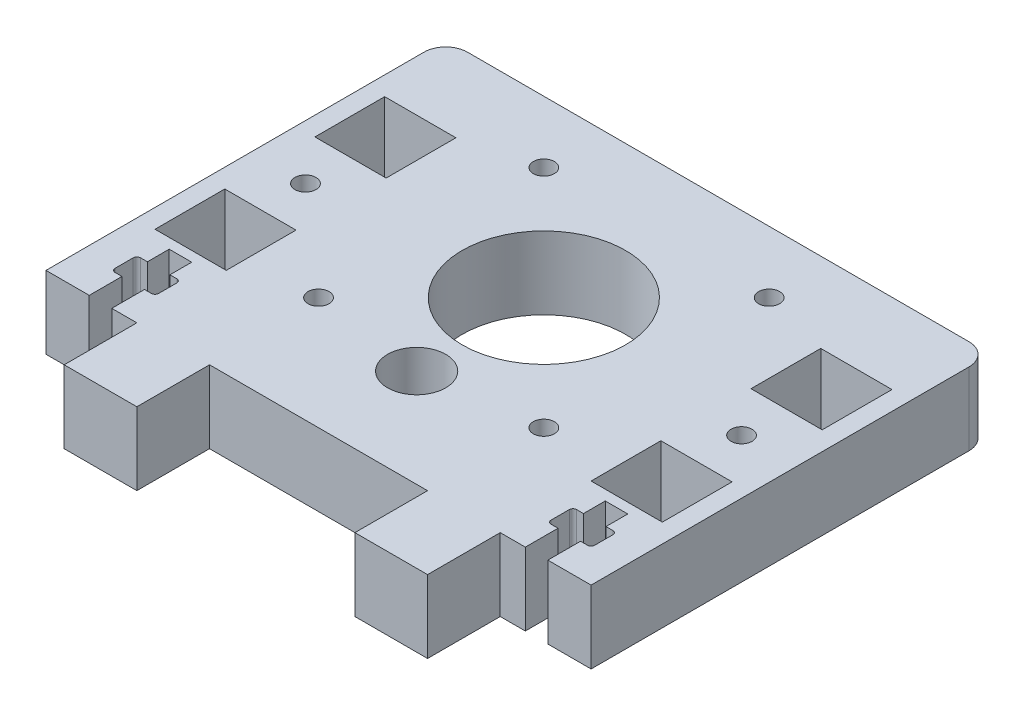
SolidWorks part; units mm, degrees
ref_plane "Front Plane" through (0, 0, 0) normal (0, 0, 1) x (1, 0, 0)
ref_plane "Top Plane" through (0, 0, 0) normal (0, 1, 0) x (1, 0, 0)
ref_plane "Right Plane" through (0, 0, 0) normal (1, 0, 0) x (0, 0, -1)
sketch "Sketch1" plane through (0, 0, 0) normal (0, 1, 0) x (1, 0, 0)
  line L0 (0, 29) -> (0, -8.5) construction
  line L1 (-34.5, 29) -> (0, 29)
  line L2 (-37.5, 26) -> (-37.5, -26)
  line L3 (-37.5, -26) -> (-25, -26)
  line L4 (0, 29) -> (0, 16.25)
  line L5 (0, -6.25) -> (0, -8.5)
  line L6 (0, -16.5) -> (0, -26) construction
  line L7 (-11.25, 5) -> (0, 5) construction
  line L8 (0, -16.5) -> (0, -26)
  line L9 (-30, 18) -> (-30, 8.4) construction
  line L10 (-37.5, 2.2) -> (0, 2.2) construction
  line L11 (-34.9, 18) -> (-25.1, 18)
  line L12 (-34.9, 18) -> (-34.9, 8.4)
  line L13 (-34.9, 8.4) -> (-25.1, 8.4)
  line L14 (-25.1, 18) -> (-25.1, 8.4)
  line L15 (-34.9, 18) -> (-25.1, 8.4) construction
  line L16 (-34.9, 8.4) -> (-25.1, 18) construction
  line L17 (-34.9, -4) -> (-25.1, -13.6) construction
  line L18 (-34.9, -13.6) -> (-25.1, -4) construction
  line L19 (-25.1, -13.6) -> (-25.1, -4)
  line L20 (-34.9, -4) -> (-25.1, -4)
  line L21 (-34.9, -13.6) -> (-34.9, -4)
  line L22 (-34.9, -13.6) -> (-25.1, -13.6)
  line L23 (-30, -4) -> (-30, -13.6) construction
  line L24 (-30, -8.8) -> (-30, 13.2) construction
  line L25 (0, 5) -> (-15.5, 20.5) construction
  line L35 (-15, -26) -> (0, -26)
  line L43 (-20, -36) -> (-20, -24.6) construction
  line L44 (-15, -26) -> (-15, -36)
  line L45 (-15, -36) -> (-25, -36)
  line L46 (-25, -36) -> (-25, -26)
  arc A1 (-34.5, 29) -> (-37.5, 26) centre (-34.5, 26) ccw
  arc A2 (0, 16.25) -> (0, -6.25) centre (0, 5) ccw
  circle A4 centre (-15.5, 20.5) radius 1.45
  circle A6 centre (-15.5, -10.5) radius 1.45
  circle A7 centre (-30, 2.2) radius 1.45
  arc A10 (0, -8.5) -> (0, -16.5) centre (0, -12.5) ccw
  point P0 (0, 0)
  point P28 (-30, 13.2)
  point P39 (-30, -8.8)
  dimension "D7" = 22.5
  dimension "D17" = 8
  dimension "D14" = 2.9
  dimension "D6" = 3
  dimension "D19" = 2.9
  dimension "D1" = 55
  dimension "D9" = 9.8
  dimension "D10" = 9.6
  dimension "D22" = 10
  dimension "D23" = 10
  dimension "D16" = 17.5
  dimension "D11" = 22
  dimension "D13" = 2.2
  dimension "D3" = 37.5
  dimension "D4" = 31
  dimension "D5" = 15.5
  dimension "D15" = 26
  dimension "D18" = 37.5
  dimension "D20" = 20
  dimension "D8" = 13.5
  dimension "D12" = 30
extrude "MainLayout" add sketch "Sketch1" along normal blind 10
sketch "Sketch2" plane through (0, 10, 0) normal (0, 1, 0) x (1, 0, 0)
  line L0 (-30, -26) -> (-30, -15) construction
  line L1 (-28.45, -21.5) -> (-28.45, -26)
  line L2 (-37.5, -26) -> (-25, -26) construction
  line L3 (-28.45, -15) -> (-31.55, -15)
  line L4 (-31.55, -15) -> (-31.55, -18)
  line L5 (-31.55, -18) -> (-32.5, -18)
  line L6 (-33, -18.5) -> (-33, -21)
  line L7 (-32.5, -21.5) -> (-31.55, -21.5)
  line L8 (-31.55, -21.5) -> (-31.55, -26)
  line L9 (-31.55, -26) -> (-28.45, -26)
  line L10 (-27.5, -21.5) -> (-28.45, -21.5)
  line L11 (-27, -18.5) -> (-27, -21)
  line L12 (-28.45, -18) -> (-27.5, -18)
  line L13 (-28.45, -15) -> (-28.45, -18)
  line L14 (0, -26) -> (0, -16.5) construction
  line L30 (-30, -26) -> (-30, -15) construction
  arc A0 (-27, -18.5) -> (-27.5, -18) centre (-27.5, -18.5) ccw
  arc A1 (-32.5, -18) -> (-33, -18.5) centre (-32.5, -18.5) ccw
  arc A2 (-27.5, -21.5) -> (-27, -21) centre (-27.5, -21) ccw
  arc A3 (-33, -21) -> (-32.5, -21.5) centre (-32.5, -21) ccw
  point P17 (0, -21.25)
  point P38 (-27, -18)
  point P41 (-33, -18)
  point P44 (-27, -21.5)
  point P47 (-33, -21.5)
  dimension "D8" = 0.5
  dimension "D1" = 1.55
  dimension "D2" = 0
  dimension "D3" = 3.5
  dimension "D5" = 11
  dimension "D6" = 3
  dimension "D4" = 8
  dimension "D7" = 30
extrude "TSlot" cut sketch "Sketch2" against normal through all
mirror "Mirror1" about plane through (0, 0, 0) normal (1, 0, 0) of "TSlot", "MainLayout"
equation "\"Y-ROD-SPACING\"=75"
equation "\"Y-BED-OFFSET\"=2"
equation "\"Y-BED-ROD-INSET\"=3.5"
equation "\"T-SLOT-NUT-FILLET-RADIUS\"=0.5"
equation "\"T-SLOT-SCREW-SHAFT-RADIUS\"=1.55"
equation "\"T-SLOT-SCREW-SHAFT-CUTOUT-LENGTH\"=11"
equation "\"T-SLOT-NUT-DEPTH\"=3.5"
equation "\"T-SLOT-NUT-WIDTH\"=2.85"
equation "\"T-SLOT-NUT-END-DISTANCE\"=8"
equation "\"ACRYLIC-TAB-CUTOUT-SIZE\"=\"ACRYLIC-THICKNESS\"+\"ACRYLIC-TAB-TOLERANCE\"*2"
equation "\"ACRYLIC-TAB-WIDTH\"=\"ACRYLIC-THICKNESS\""
equation "\"ACRYLIC-M3-HOLE\"=2.9"
equation "\"SMOOTHROD-CAP-SCREW-DISTANCE\"=20"
equation "\"FRAME-WIDTH-INNER\"=370"
equation "\"NEMA17-HOLE-SPACING\"=31"
equation "\"NEMA17-CENTRAL-CUTOUT\"=22.5"
equation "\"D7@Sketch1\"=\"NEMA17-CENTRAL-CUTOUT\""
equation "\"D5@Sketch1\"=\"NEMA17-HOLE-SPACING\"/2"
equation "\"D4@Sketch1\"=\"NEMA17-HOLE-SPACING\""
equation "\"D19@Sketch1\"=\"ACRYLIC-M3-HOLE\""
equation "\"D14@Sketch1\"=\"ACRYLIC-M3-HOLE\""
equation "\"D9@Sketch1\"=\"ACRYLIC-THICKNESS\"-\"KERF\"*2"
equation "\"D10@Sketch1\"=\"ACRYLIC-TAB-WIDTH\"-\"KERF\"*4"
equation "\"D23@Sketch1\"=\"ACRYLIC-TAB-WIDTH\""
equation "\"D22@Sketch1\"=\"ACRYLIC-TAB-WIDTH\""
equation "\"D5@Sketch2\"=\"T-SLOT-SCREW-SHAFT-CUTOUT-LENGTH\""
equation "\"D4@Sketch2\"=\"T-SLOT-NUT-END-DISTANCE\""
equation "\"D3@Sketch2\"=\"T-SLOT-NUT-DEPTH\""
equation "\"D1@Sketch2\"=\"T-SLOT-SCREW-SHAFT-RADIUS\""
equation "\"D8@Sketch2\"=\"T-SLOT-NUT-FILLET-RADIUS\""
equation "\"Z-BRACKET-REACH\"=55"
equation "\"D1@Sketch1\"=\"Z-BRACKET-REACH\""
equation "\"Z-ROD-SPACING\"=17.5"
equation "\"ACRYLIC-THICKNESS\"=10"
equation "\"TOP-BRACKET-SPACING\"=40"
equation "\"SMOOTHROD-X-LENGTH\"=350"
equation "\"SMOOTHROD-Y-LENGTH\"=350"
equation "\"SMOOTHROD-Z-LENGTH\"=350"
equation "\"SMOOTHROD-TIGHTENING-HEADROOM\"=.25"
equation "\"LEADSCREW-Z-LENGTH\"=300"
equation "\"D16@Sketch1\"=\"Z-ROD-SPACING\""
equation "\"X-ROD-SPACING\"=45"
equation "\"ACRYLIC-THICKNESS2\"=4.5"
equation "\"SCREW-LENGTH-FRAME\"=\"ACRYLIC-THICKNESS\" + 10"
equation "\"SCREW-HEAD-RADIUS\"=6"
equation "\"PRINTED-X-SMOOTHROD-DIAMETER\"=9.0"
equation "\"PRINTED-X-SMOOTHROD-CUTOUT\"=10"
equation "\"PRINTED-X-BASE-HEIGHT\"=10"
equation "\"PRINTED-LM8UU-CUTOUT-SIZE\"=15.5"
equation "\"PRINTED-LM8UU-CUTOUT-LENGTH\"=24.5"
equation "\"PRINTED-X-IDLER-HEIGHT\"=16"
equation "\"PSU-MOUNTING-WIDTH\"=95"
equation "\"PSU-MOUNTING-HEIGHT\"=177"
equation "\"D1@MainLayout\"=\"ACRYLIC-THICKNESS\""
equation "\"Z-ROD-INSET\"=13.5"
equation "\"Y-BELT-TO-ROD-DISTANCE\"=20"
equation "\"SPOOL-HOLDER-ROD-SPACING\"=150"
equation "\"D8@Sketch1\"=\"Z-ROD-INSET\""
equation "\"Y-BED-SCREW-SPACING\"=209"
equation "\"Y-BED-SCREW-CUTOUT-SLOT-HEIGHT\"=2"
equation "\"ACRYLIC-TAB-TOLERANCE\"=-.05"
equation "\"SCREW-LENGTH-MOTOR\"=\"ACRYLIC-THICKNESS\" + 5"
equation "\"SCREW-LENGTH-EXTRUDER\"=28"
equation "\"ACRYLIC-X-CARRIAGE-WIDTH\"=55"
equation "\"ACRYLIC-X-CARRIAGE-HEIGHT\"=75"
equation "\"ACRYLIC-X-CARRIAGE-LM8UU-CUTOUT-WIDTH\"=24.25"
equation "\"ACRYLIC-X-CARRIAGE-SCREW-SPACING-X\"=15"
equation "\"ACRYLIC-X-CARRIAGE-SCREW-SPACING-Y\"=33"
equation "\"ACRYLIC-X-CARRIAGE-CENTER-TAB-SPACING\"=14"
equation "\"ACRYLIC-X-CARRIAGE-EXTRUDER-OFFSET\"=26"
equation "\"ACRYLIC-X-CARRIAGE-EXTRUDER-ANGLE\"=90"
equation "\"ACRYLIC-X-CARRIAGE-EXTRUDER-SHELF-DEPTH\"=\"ACRYLIC-X-CARRIAGE-EXTRUDER-OFFSET\" + 28"
equation "\"ACRYLIC-X-CARRIAGE-EXTRUDER-BRACE-SPACING\"=23"
equation "\"ACRYLIC-X-CARRIAGE-EXTRUDER-BRACE-TAB-OFFSET\"=20"
equation "\"ACRYLIC-X-CARRIAGE-EXTRUDER-BRACE-HEIGHT\"=35"
equation "\"ACRYLIC-X-CARRIAGE-EXTRUDER-BRACE-SCREW-SPACING\"=22"
equation "\"KERF\"=0.1"
equation "\"PRINTED-M3-HOLE\"=3.5"
equation "\"PRINTED-M3-NUT-AF\"=6.25"
equation "\"ACRYLIC-X-CARRIAGE-LM8UU-CUTOUT-HEIGHT\"=11.0"
equation "\"ACRYLIC-X-CARRIAGE-DUAL-WIDTH-MULTIPLIER\"=1.65"
equation "\"ACRYLIC-X-CARRIAGE-DUAL-HOTEND-SPACING\"=42"
equation "\"ACRYLIC-X-CARRIAGE-DUAL-WIDTH\"=75"
equation "\"ACRYLIC-X-CARRIAGE-DUAL-FAN-OFFSET\"=52"
equation "\"ACRYLIC-X-CARRIAGE-DUAL-FAN-HEIGHT\"=20"
equation "\"ACRYLIC-X-CARRIAGE-DUAL-HOTEND-SEPARATION\"=36"
equation "\"ACRYLIC-X-CARRIAGE-DUAL-MOUNT-PLATE-DEPTH\"=75"
equation "\"ACRYLIC-X-CARRIAGE-DUAL-MOUNT-BRACE-WIDTH\"=33"
equation "\"ACRYLIC-X-CARRIAGE-DUAL-MOUNT-SCREW-WIDTH\"=40"
equation "\"BLOWER-FAN-WIDTH\"=15"
